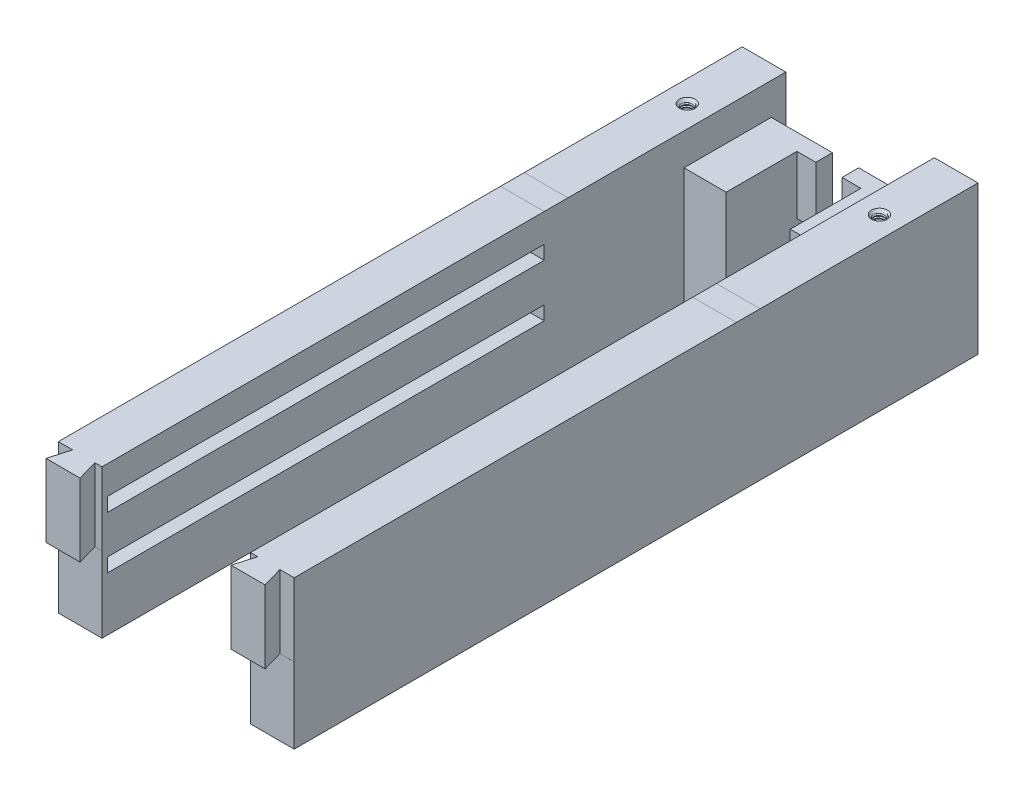
SolidWorks part; units mm, degrees
ref_plane "Front Plane" through (0, 0, 0) normal (0, 0, 1) x (1, 0, 0)
ref_plane "Top Plane" through (0, 0, 0) normal (0, 1, 0) x (1, 0, 0)
ref_plane "Right Plane" through (0, 0, 0) normal (1, 0, 0) x (0, 0, -1)
sketch "Sketch1" plane through (0, 0, 0) normal (1, 0, 0) x (0, 0, -1)
  line L1 (-64.5621, 30.5573) -> (177.4379, 30.5573)
  line L2 (-64.5621, 30.5573) -> (-64.5621, -20.4427)
  line L3 (-64.5621, -20.4427) -> (177.4379, -20.4427)
  line L4 (177.4379, 30.5573) -> (177.4379, -20.4427)
  dimension "D1" = 242
  dimension "D2" = 51
extrude "Boss-Extrude1" add sketch "Sketch1" along normal blind 15 contours L2 L3 L4 L1
sketch "Sketch26" plane through (0, 0, 0) normal (-1, 0, 0) x (0, 0, 1)
  line L1 (-172.4379, 19.5573) -> (-142.4379, 19.5573)
  line L2 (-172.4379, 19.5573) -> (-172.4379, -20.4427)
  line L3 (-172.4379, -20.4427) -> (-142.4379, -20.4427)
  line L4 (-142.4379, 19.5573) -> (-142.4379, -20.4427)
  line L5 (64.5621, -20.4427) -> (-177.4379, -20.4427) construction
  line L6 (-177.4379, 30.5573) -> (-177.4379, -20.4427) construction
  dimension "D1" = 5
  dimension "D2" = 30
  dimension "D3" = 40
extrude "Boss-Extrude3" add sketch "Sketch26" against normal blind 29.5
sketch "Sketch28" plane through (29.5, 0, 0) normal (1, 0, 0) x (0, 0, -1)
  line L0 (147.0417, -20.4427) -> (147.0417, -10.6927)
  line L1 (172.4379, -20.4427) -> (142.4379, -20.4427) construction
  line L2 (147.0417, -10.6927) -> (162.0417, -10.6927)
  line L3 (162.0417, -10.6927) -> (162.0417, -20.4427)
  line L4 (162.0417, -20.4427) -> (147.0417, -20.4427)
  dimension "D1" = 9.75
  dimension "D2" = 15
extrude "Boss-Extrude5" add sketch "Sketch28" along normal blind 4.5
sketch "Sketch29" plane through (29.5, 0, 0) normal (1, 0, 0) x (0, 0, -1)
  line L0 (172.4379, 19.5573) -> (166.7379, 19.5573)
  line L1 (142.4379, 19.5573) -> (172.4379, 19.5573) construction
  line L2 (166.7379, 19.5573) -> (166.7379, -0.4427)
  line L3 (166.7379, -0.4427) -> (172.4379, -0.4427)
  line L4 (172.4379, 19.5573) -> (172.4379, -20.4427) construction
  line L5 (172.4379, -0.4427) -> (172.4379, 19.5573)
  dimension "D1" = 20
  dimension "D2" = 5.7
extrude "Boss-Extrude6" add sketch "Sketch29" along normal blind 6.5
sketch "Sketch12" plane through (0, 30.5573, 0) normal (0, 1, 0) x (1, 0, 0)
  line L0 (0, -57.4487) -> (4.9097, -57.4487)
  line L1 (0, -64.5621) -> (0, 177.4379) construction
  line L2 (4.9097, -57.4487) -> (2.87, -64.5621)
  line L3 (15, -64.5621) -> (0, -64.5621) construction
  line L4 (2.87, -64.5621) -> (0, -64.5621)
  line L5 (0, -64.5621) -> (0, -57.4487)
  line L6 (15, -57.4487) -> (15, -64.5621)
  line L7 (15, -64.5621) -> (15, 177.4379) construction
  line L8 (15, -64.5621) -> (14.57, -64.5621)
  line L9 (14.57, -64.5621) -> (12.5303, -57.4487)
  line L10 (12.5303, -57.4487) -> (15, -57.4487)
  dimension "D1" = 7.4
  dimension "D2" = 7.4
  dimension "D3" = 106
  dimension "D4" = 106
  dimension "D5" = 11.7
  dimension "D6" = 2.87
extrude "Cut-Extrude8" cut sketch "Sketch12" against normal blind 25
sketch "Sketch13" plane through (0, -20.4427, 0) normal (0, -1, 0) x (1, 0, 0)
  line L0 (15, 64.5621) -> (15, -142.4379) construction
  line L1 (0, 64.5621) -> (15, 64.5621)
  line L2 (0, 64.5621) -> (0, 57.4521)
  line L3 (0, 57.4521) -> (15, 57.4521)
  line L4 (15, 64.5621) -> (15, 57.4521)
  dimension "D1" = 7.11
extrude "Cut-Extrude9" cut sketch "Sketch13" against normal blind 26
sketch "Sketch17" plane through (0, 30.5573, 0) normal (0, 1, 0) x (1, 0, 0)
  line L0 (15, -57.4487) -> (15, 177.4379) construction
  line L1 (0, 110.4379) -> (15, 110.4379)
  line L2 (0, 110.4379) -> (0, 102.5879)
  line L3 (0, 102.5879) -> (15, 102.5879)
  line L4 (15, 110.4379) -> (15, 102.5879)
  line L6 (0, 102.5879) -> (15, 102.5879)
  line L7 (0, 102.5879) -> (0, 94.4379)
  line L8 (0, 94.4379) -> (15, 94.4379)
  line L9 (15, 102.5879) -> (15, 94.4379)
  line M14 (15, -57.4487) -> (15, 177.4379)
  line M16 (0, 177.4379) -> (0, -57.4487)
  dimension "D1" = 7.85
  dimension "D2" = 8.15
extrude "Cut-Extrude10" cut sketch "Sketch17" against normal blind 0.0001 contours L8 L3 M16 M14
sketch "Sketch7" plane through (0, 0, -94.4379) normal (0, 0, -1) x (-1, 0, 0)
  line L0 (-15, -20.4427) -> (-15, -1.9427)
  line L1 (-15, 2.8073) -> (-15, 16.0573)
  line L2 (-10.25, 2.8073) -> (-15, 2.8073)
  line L3 (-10.25, 2.8073) -> (-10.25, -1.9427)
  line L4 (-10.25, -1.9427) -> (-15, -1.9427)
  line L5 (-15, 2.8073) -> (-15, -1.9427)
  line L6 (-15, 30.5573) -> (-15, -20.4427) construction
  line L8 (-15, 16.0573) -> (-10.25, 16.0573)
  line L9 (-15, 16.0573) -> (-15, 20.8073)
  line L10 (-15, 20.8073) -> (-10.25, 20.8073)
  line L11 (-10.25, 16.0573) -> (-10.25, 20.8073)
  dimension "D1" = 18.5
  dimension "D2" = 4.75
  dimension "D3" = 4.75
  dimension "D4" = 13.25
  dimension "D5" = 4.75
  dimension "D6" = 4.75
extrude "Cut-Extrude5" cut sketch "Sketch7" against normal blind 150
sketch "Sketch22" plane through (0, 30.5573, 0) normal (0, 1, 0) x (1, 0, 0)
  line L0 (15, 177.4379) -> (15, 161.9379)
  line L1 (15, 102.5879) -> (15, 177.4379) construction
  line L3 (15, 161.9379) -> (8, 161.9379)
  line L4 (15, 161.9379) -> (15, 158.7879)
  line L5 (15, 158.7879) -> (8, 158.7879)
  line L6 (8, 161.9379) -> (8, 158.7879)
  line M5 (15, 102.5879) -> (15, 177.4379)
  dimension "D1" = 15.5
  dimension "D2" = 7
  dimension "D3" = 3.15
extrude "Cut-Extrude13" [suppressed] cut sketch "Sketch22" against normal blind 45 contours L3 L6 L5 M5
ref_plane "Plane1" through (40.5, 0, 0) normal (1, 0, 0) x (0, 0, -1)
sketch "Sketch18" [suppressed] plane through (0, 30.5573, 0) normal (0, 1, 0) x (1, 0, 0)
  line L0 (15, 102.5879) -> (15, 136.5879)
  line L1 (15, 102.5879) -> (15, 177.4379) construction
  line L3 (15, 136.5879) -> (10, 136.5879)
  line L4 (15, 136.5879) -> (15, 144.0879)
  line L5 (15, 144.0879) -> (10, 144.0879)
  line L6 (10, 136.5879) -> (10, 144.0879)
  line M6 (15, 102.5879) -> (15, 177.4379)
  dimension "D1" = 34
  dimension "D2" = 5
  dimension "D3" = 7.5
extrude "Cut-Extrude11" [suppressed] cut sketch "Sketch18" against normal blind 38 contours L6 L3 L5 M6
sketch "Sketch23" [suppressed] plane through (0, 0, -177.4379) normal (0, 0, -1) x (-1, 0, 0)
  line L0 (-15, -20.4427) -> (-15, 9.0573)
  line L1 (-15, 30.5573) -> (-15, -20.4427) construction
  line L3 (-15, 9.0573) -> (-10.5, 9.0573)
  line L4 (-15, 9.0573) -> (-15, 13.5573)
  line L5 (-15, 13.5573) -> (-10.5, 13.5573)
  line L6 (-10.5, 9.0573) -> (-10.5, 13.5573)
  line M5 (-15, 30.5573) -> (-15, -20.4427)
  dimension "D1" = 4.5
  dimension "D2" = 4.5
  dimension "D3" = 29.5
extrude "Cut-Extrude14" [suppressed] cut sketch "Sketch23" against normal blind 45 contours L3 L6 L5 M5
mirror "Mirror4" about plane through (40.5, 0, 0) normal (1, 0, 0) of bodies 107 113
sketch "Sketch30" plane through (0, 30.5573, 0) normal (0, 1, 0) x (1, 0, 0)
  circle A0 centre (73.5, 151.0787) radius 2
  circle A1 centre (7.5, 151.0787) radius 2
hole_wizard "#8-32 Tapped Hole1" positions "Sketch35" profile "Sketch37" tap size "#8-32" standard "ANSI Inch"
sketch "Sketch35" plane through (0, 30.5573, 0) normal (0, 1, 0) x (1, 0, 0)
  point P0 (7.5, 151.0787)
  point P3 (73.5, 151.0787)
sketch "Sketch37" plane through (7.5, 30.5573, -151.0787) normal (1, 0, 0) x (0, 0, 1)
  line L0 (0, 0) -> (0, 10.7074)
  line L1 (0, 10.7074) -> (1.7272, 9.6696)
  line L2 (1.7272, 9.6696) -> (1.7272, 0.9906)
  line L3 (1.7272, 0.9906) -> (2.7178, 0)
  line L5 (2.7178, 0) -> (0, 0)
  line L6 (-1.7272, 0.9906) -> (-2.7178, 0) construction
  line L10 (0, 10.7074) -> (-1.7272, 9.6696) construction
  line L11 (0, -6.35) -> (0, 107.95) construction
  dimension "Tap Drill Dia." = 3.4544
  dimension "Tap Drill Depth" = 10.7074
  dimension "Near C'Sink Dia." = 5.4356
  dimension "Near C'Sink Angle" = 90
  dimension "Drill Angle" = 118
cosmetic thread "Hole Thread1" parameters "D1"=8.33, "D2"=4.1656
cosmetic thread "Hole Thread2" parameters "D1"=8.33, "D2"=4.1656
thread "Thread3" pitch 0.7937 start angle 0, offset 1, length 10, pitch 0.7937, diameter 3.4544
ref_plane "Plane6" through (5.7728, 30.5667, -151.0787) normal (0, 0, 1) x (-1, 0, 0)
sketch "Thread Profile5" plane through (5.7728, 30.5667, -151.0787) normal (0, 0, 1) x (-1, 0, 0)
  line L0 (0, 0) -> (0, 0.7937) construction
  line L1 (0, 0) -> (0.4296, 0.248)
  line L2 (0.4296, 0.248) -> (0.4296, 0.3473)
  line L3 (0.4296, 0.3473) -> (0, 0.5953)
  line L4 (0.4296, 0.2977) -> (0, 0.2977) construction
  line L11 (0, 0) -> (0, 0.5953)
  point P2 (0, 0)
  dimension "Pitch" = 0.7937
  dimension "Profile_Angle" = 60
  dimension "Profile_Land" = 0.0992
  dimension "Profile_Height" = 0.4296
thread "Thread4" pitch 0.7937 profile "Thread Profile6" start angle 0, offset 1, length 10, pitch 0.7937, diameter 3.4544
ref_plane "Plane7" through (71.7728, 30.5667, -151.0787) normal (0, 0, 1) x (-1, 0, 0)
sketch "Thread Profile6" plane through (71.7728, 30.5667, -151.0787) normal (0, 0, 1) x (-1, 0, 0)
  line L0 (0, 0) -> (0, 0.7937) construction
  line L1 (0, 0) -> (0.4296, 0.248)
  line L2 (0.4296, 0.248) -> (0.4296, 0.3473)
  line L3 (0.4296, 0.3473) -> (0, 0.5953)
  line L4 (0.4296, 0.2977) -> (0, 0.2977) construction
  line L11 (0, 0) -> (0, 0.5953)
  point P2 (0, 0)
  dimension "Pitch" = 0.7937
  dimension "Profile_Angle" = 60
  dimension "Profile_Land" = 0.0992
  dimension "Profile_Height" = 0.4296
